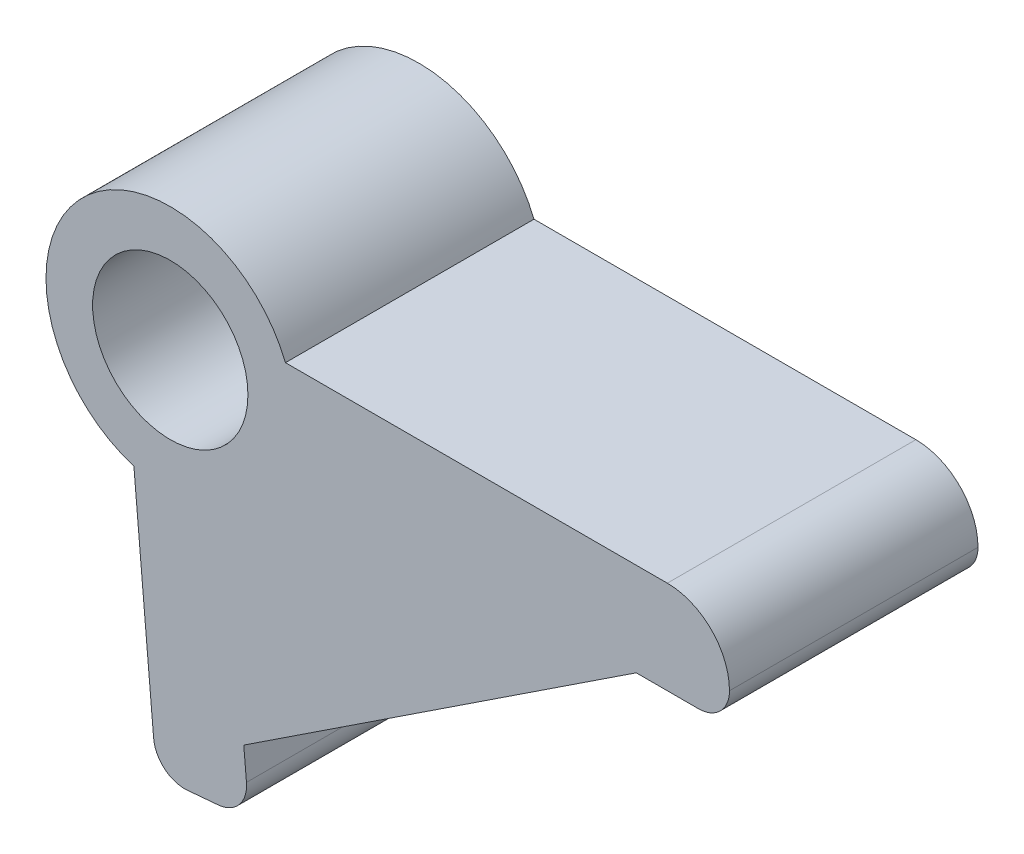
SolidWorks part; units mm, degrees
ref_plane "Front Plane" through (0, 0, 0) normal (0, 0, 1) x (1, 0, 0)
ref_plane "Top Plane" through (0, 0, 0) normal (0, 1, 0) x (1, 0, 0)
ref_plane "Right Plane" through (0, 0, 0) normal (1, 0, 0) x (0, 0, -1)
sketch "Sketch1" plane through (0, 0, 0) normal (0, 0, 1) x (1, 0, 0)
  line L0 (0, 0) -> (0, 10.942) construction
  line L1 (0, 0) -> (1.0459, -11.9543) construction
  line L2 (1.0459, -11.9543) -> (-0.4484, -12.0851)
  line L3 (-0.4484, -12.0851) -> (-1.1711, -3.8247)
  line L5 (1.8175, -3.5633) -> (2.5402, -11.8236)
  line L6 (2.5402, -11.8236) -> (1.0459, -11.9543)
  line L7 (0, 0) -> (18, 0) construction
  line L8 (15, -1.5) -> (2.3658, -9.8312)
  line L9 (3.7081, 1.5) -> (18, 1.5)
  line L11 (3.7081, -1.5) -> (18, -1.5)
  line L12 (18, 1.5) -> (18, -1.5)
  circle A0 centre (0, 0) radius 2.5
  arc A1 (3.7081, 1.5) -> (-1.1711, -3.8247) centre (0, 0) ccw
  arc A2 (1.8175, -3.5633) -> (3.7081, -1.5) centre (0, 0) ccw
  point P7 (0, 0)
  point P8 (2.4182, -10.4301)
  point P18 (0, 0)
  dimension "D1" = 5
  dimension "D6" = 8
  dimension "D2" = 18
  dimension "D3" = 12
  dimension "D4" = 3
  dimension "D5" = 3
  dimension "D7" = 85
  dimension "D8" = 3
  dimension "D9" = 2
extrude "Boss-Extrude1" add sketch "Sketch1" along normal blind 8 contours A2 L5 L8 L11 | A0 | L2 L3 A1 L9 L12 L11 A2 L5 L6 region at (6.5245, -4.3762, 0) region at (0, 0, 0)
fillet "Fillet1" radius 1 3 edges at (-0.4484, -12.0851, 4) (2.5402, -11.8236, 4) (18, -1.5, 4)
fillet "Fillet2" radius 2 1 edges at (18, 1.5, 4)
